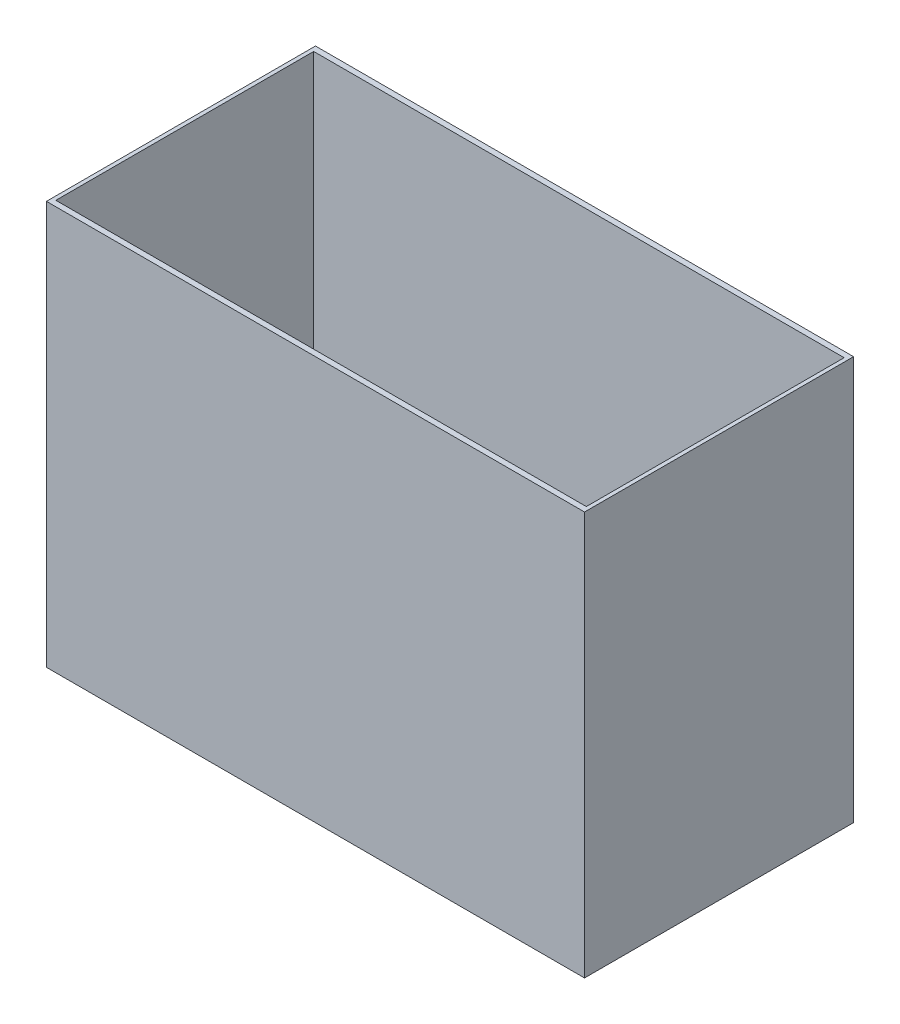
SolidWorks part; units mm, degrees
ref_plane "Front Plane" through (0, 0, 0) normal (0, 0, 1) x (1, 0, 0)
ref_plane "Top Plane" through (0, 0, 0) normal (0, 1, 0) x (1, 0, 0)
ref_plane "Right Plane" through (0, 0, 0) normal (1, 0, 0) x (0, 0, -1)
other "Bounding Box"
ref_plane "Default Plane" through (-292.1, 0, -139.7) normal (0, 1, 0) x (1, 0, 0)
sketch "Sketch1" plane through (0, 0, 0) normal (0, 1, 0) x (1, 0, 0)
  line L0 (-292.1, 0) -> (292.1, 0) construction
  line L1 (-292.1, 139.7) -> (292.1, 139.7)
  line L2 (-292.1, 139.7) -> (-292.1, -139.7)
  line L3 (-292.1, -139.7) -> (292.1, -139.7)
  line L4 (292.1, 139.7) -> (292.1, -139.7)
  line L5 (0, 139.7) -> (0, -139.7) construction
  point P8 (0, 0)
  dimension "D1" = 584.2
  dimension "D2" = 279.4
extrude "Boss-Extrude1" add sketch "Sketch1" along normal blind 6.35
sketch "Sketch2" plane through (0, 6.35, 0) normal (0, 1, 0) x (1, 0, 0)
  line L0 (-245.9259, -63.5) -> (-55.3589, -63.5) construction
  line L1 (-241.3, -120.6497) -> (-152.4, -120.6497)
  line L2 (-241.3, -120.6497) -> (-241.3, -101.5997)
  line L3 (-241.3, -101.5997) -> (-152.4, -101.5997)
  line L4 (-152.4, -120.6497) -> (-152.4, -101.5997)
  line L5 (-241.3, -120.6497) -> (-152.4, -101.5997) construction
  line L6 (-241.3, -101.5997) -> (-152.4, -120.6497) construction
  line L7 (-292.1, 139.7) -> (-292.1, -139.7) construction
  line L8 (-292.1, 0) -> (292.1, 0) construction
  line L9 (292.1, -139.7) -> (292.1, 139.7) construction
  line L10 (0, 0) -> (0, 121.6784) construction
  line L11 (241.3, -101.5997) -> (152.4, -120.6497) construction
  line L12 (241.3, -120.6497) -> (152.4, -101.5997) construction
  line L13 (152.4, -120.6497) -> (152.4, -101.5997)
  line L14 (241.3, -101.5997) -> (152.4, -101.5997)
  line L15 (241.3, -120.6497) -> (241.3, -101.5997)
  line L16 (241.3, -120.6497) -> (152.4, -120.6497)
  point P0 (-196.85, -111.1247)
  point P17 (196.85, -111.1247)
  dimension "D1" = 19.05
  dimension "D2" = 88.9
  dimension "D3" = 38.0997
  dimension "D4" = 50.8
  dimension "D5" = 63.5
extrude "Boss-Extrude2" [suppressed] add sketch "Sketch2" along normal blind 304.8 separate body contours L2 L1 L4 L3
pattern_linear "LPattern1" [suppressed] count 2 spacing 304.8 of bodies 101
pattern_linear "LPattern2" [suppressed] count 2 spacing 215.9 of bodies 101
sketch "Sketch3" plane through (0, 0, 0) normal (0, 1, 0) x (1, 0, 0)
  line L1 (-304.8, -152.4) -> (304.8, -152.4)
  line L2 (-304.8, -152.4) -> (-304.8, 152.4)
  line L3 (-304.8, 152.4) -> (304.8, 152.4)
  line L4 (304.8, -152.4) -> (304.8, 152.4)
  line L5 (-304.8, -152.4) -> (304.8, 152.4) construction
  line L6 (-304.8, 152.4) -> (304.8, -152.4) construction
  line L7 (-300.482, -146.05) -> (300.482, -146.05)
  line L8 (-300.482, -146.05) -> (-300.482, 146.05)
  line L9 (-300.482, 146.05) -> (300.482, 146.05)
  line L10 (300.482, -146.05) -> (300.482, 146.05)
  line L11 (-300.482, -146.05) -> (300.482, 146.05) construction
  line L12 (-300.482, 146.05) -> (300.482, -146.05) construction
  point P0 (0, 0)
  point P6 (0, 0)
  dimension "D1" = 609.6
  dimension "D2" = 304.8
  dimension "D3" = 292.1
  dimension "D4" = 600.964
extrude "Boss-Extrude3" add sketch "Sketch3" along normal blind 457.2 separate body
sketch "Sketch4" plane through (0, 6.35, 0) normal (0, 1, 0) x (1, 0, 0)
  line L0 (292.1, -139.7) -> (292.1, 139.7) construction
  line L1 (238.8561, 120.65) -> (261.8611, 120.65) construction
  line L2 (273.05, 95.4723) -> (273.05, 121.6668) construction
  line L3 (292.1, 139.7) -> (-292.1, 139.7) construction
  circle A3 centre (252.0119, 99.6119) radius 21.0381
  dimension "D1" = 42.0762
  dimension "D2" = 19.05
  dimension "D3" = 19.05
extrude "Cut-Extrude1" cut sketch "Sketch4" against normal through all
sketch "Sketch7" plane through (0, 6.35, 0) normal (0, 1, 0) x (1, 0, 0)
  line L0 (292.1, 0) -> (49.4912, 0) construction
  line L1 (292.1, -139.7) -> (292.1, 139.7) construction
  circle A0 centre (190.5, 0) radius 4 construction
  circle A1 centre (190.5, 0) radius 2.7781
  dimension "D1" = 8
  dimension "D2" = 5.5562
  dimension "D3" = 101.6
extrude "Cut-Extrude3" cut sketch "Sketch7" against normal through all
sketch "Sketch8" plane through (0, 6.35, 0) normal (0, 1, 0) x (1, 0, 0)
  circle A0 centre (94.9, -12.8415) radius 1.9844 construction
  circle A1 centre (146.1, -12.8415) radius 1.9844 construction
  circle A2 centre (146.1, 12.8415) radius 1.9844 construction
  circle A3 centre (94.9, 12.8415) radius 1.9844 construction
  circle A4 centre (94.9, -12.8415) radius 1.9844
  circle A5 centre (146.1, -12.8415) radius 1.9844
  circle A6 centre (146.1, 12.8415) radius 1.9844
  circle A7 centre (94.9, 12.8415) radius 1.9844
extrude "Cut-Extrude4" cut sketch "Sketch8" against normal through all
sketch "Sketch9" plane through (0, 0, 0) normal (0, -1, 0) x (1, 0, 0)
  circle A1 centre (190.5, 0) radius 6.35
  circle A2 centre (146.1, 12.8415) radius 6.35
  circle A3 centre (94.9, 12.8415) radius 6.35
  circle A4 centre (94.9, -12.8415) radius 6.35
  circle A5 centre (146.1, -12.8415) radius 6.35
sketch "Sketch11" plane through (0, 0, 0) normal (0, -1, 0) x (1, 0, 0)
  line L0 (-292.1, 139.7) -> (292.1, 139.7) construction
  line L1 (215.9, 139.7) -> (165.1, 139.7)
  line L2 (215.9, 139.7) -> (215.9, 136.525)
  line L3 (215.9, 136.525) -> (165.1, 136.525)
  line L4 (165.1, 139.7) -> (165.1, 136.525)
  line L5 (292.1, 139.7) -> (292.1, -139.7) construction
  dimension "D1" = 3.175
  dimension "D2" = 50.8
  dimension "D3" = 76.2
extrude "Cut-Extrude6" cut sketch "Sketch11" against normal through all
mirror "Mirror2" about plane through (0, 0, 0) normal (0, 0, 1) of "Cut-Extrude1", "Cut-Extrude6"
sketch "Sketch12" plane through (0, 6.35, 0) normal (0, 1, 0) x (1, 0, 0)
  line L0 (292.1, -17.78) -> (285.75, -17.78) construction
  line L1 (292.1, -43.18) -> (285.75, -43.18) construction
  line L2 (285.75, -43.18) -> (285.75, -17.78) construction
  line L3 (292.1, -78.74) -> (285.75, -78.74) construction
  line L4 (292.1, -104.14) -> (285.75, -104.14) construction
  line L5 (285.75, -78.74) -> (285.75, -104.14) construction
  line L6 (292.1, -17.78) -> (285.75, -17.78)
  line L7 (292.1, -43.18) -> (285.75, -43.18)
  line L8 (285.75, -43.18) -> (285.75, -17.78)
  line L9 (292.1, -78.74) -> (285.75, -78.74)
  line L10 (292.1, -104.14) -> (285.75, -104.14)
  line L11 (285.75, -78.74) -> (285.75, -104.14)
  line L12 (292.1, 0) -> (257.5404, 0) construction
  line L13 (285.75, 78.74) -> (285.75, 104.14)
  line L14 (292.1, 104.14) -> (285.75, 104.14)
  line L15 (292.1, 78.74) -> (285.75, 78.74)
  line L16 (285.75, 43.18) -> (285.75, 17.78)
  line L17 (292.1, 43.18) -> (285.75, 43.18)
  line L18 (292.1, 17.78) -> (285.75, 17.78)
  line L19 (292.1, -139.7) -> (292.1, 139.7) construction
  line L20 (292.1, -104.14) -> (292.1, -78.74)
  line L21 (292.1, -43.18) -> (292.1, -17.78)
  line L22 (292.1, 17.78) -> (292.1, 43.18)
  line L23 (292.1, 78.74) -> (292.1, 104.14)
extrude "Cut-Extrude7" cut sketch "Sketch12" against normal through all
sketch "Sketch13" plane through (0, 6.35, 0) normal (0, 1, 0) x (1, 0, 0)
  line L0 (252.0119, -99.6119) -> (133.5003, -46.1866) construction
  line L1 (210.6176, 12.194) -> (133.5003, -46.1866) construction
  line L2 (252.0119, 99.6119) -> (210.6176, 12.194) construction
  line L3 (257.6906, -66.7163) -> (23.4514, -66.7163) construction
  circle A0 centre (252.0119, -99.6119) radius 21.0381 construction
  circle A1 centre (252.0119, -99.6119) radius 21.0381 construction
  circle A2 centre (133.5003, -46.1866) radius 21.0381
  circle A3 centre (210.6176, 12.194) radius 21.0381
  circle A4 centre (252.0119, 99.6119) radius 21.0381 construction
  circle A5 centre (252.0119, 99.6119) radius 21.0381 construction
  circle A6 centre (210.6176, 12.194) radius 55.7022 construction
  point P9 (135.4762, -42.0037)
  point P11 (0, 0)
  point P15 (133.5003, -46.1866)
  dimension "D1" = 129.9972
  dimension "D3" = 111.4044
  dimension "D2" = 96.7232
  dimension "D4" = 96.7232
extrude "Cut-Extrude8" cut sketch "Sketch13" against normal through all
sketch "Sketch14" plane through (0, 6.35, 0) normal (0, 1, 0) x (1, 0, 0)
  circle A1 centre (45.3035, 4.219) radius 4.7113 construction
  circle A2 centre (45.3035, 4.219) radius 2.7781
  dimension "D1" = 5.5562
extrude "Cut-Extrude9" cut sketch "Sketch14" against normal through all
